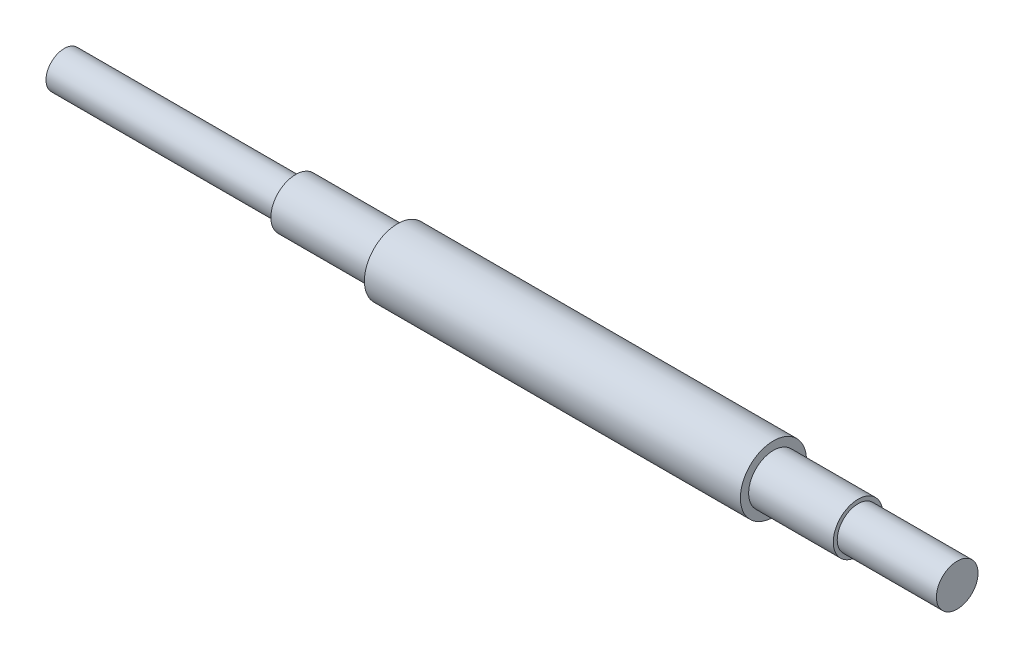
SolidWorks part; units mm, degrees
material "Plain Carbon Steel"
ref_plane "Front Plane" through (0, 0, 0) normal (0, 0, 1) x (1, 0, 0)
ref_plane "Top Plane" through (0, 0, 0) normal (0, 1, 0) x (1, 0, 0)
ref_plane "Right Plane" through (0, 0, 0) normal (1, 0, 0) x (0, 0, -1)
sketch "Sketch1" plane through (0, 0, 0) normal (0, 1, 0) x (1, 0, 0)
  line L0 (-78.6306, 0) -> (92.9034, 0) construction
  line L1 (-78.6306, 0) -> (-78.6306, 3.5)
  line L2 (-78.6306, 3.5) -> (-34.1806, 3.5)
  line L3 (-34.1806, 3.5) -> (-34.1806, 4.7625)
  line L4 (-34.1806, 4.7625) -> (-14.6226, 4.7625)
  line L5 (-14.6226, 4.7625) -> (-14.6226, 6.35)
  line L6 (-14.6226, 6.35) -> (57.5974, 6.35)
  line L7 (57.5974, 6.35) -> (57.5974, 4.7625)
  line L8 (57.5974, 4.7625) -> (73.8534, 4.7625)
  line L9 (73.8534, 4.7625) -> (73.8534, 3.9992)
  line L10 (73.8534, 3.9992) -> (92.9034, 3.9992)
  line L11 (92.9034, 3.9992) -> (92.9034, 0)
  line L12 (-78.6306, 0) -> (92.9034, 0)
  line L13 (-97.9506, 0) -> (194.5593, 0) construction
  dimension "D1" = 7
  dimension "D2" = 9.525
  dimension "D3" = 9.525
  dimension "D4" = 7.9985
  dimension "D5" = 44.45
  dimension "D6" = 19.558
  dimension "D7" = 16.256
  dimension "D8" = 19.05
  dimension "D9" = 72.22
  dimension "D10" = 6.35
revolve "Revolve1" add sketch "Sketch1" angle 360 about L13
